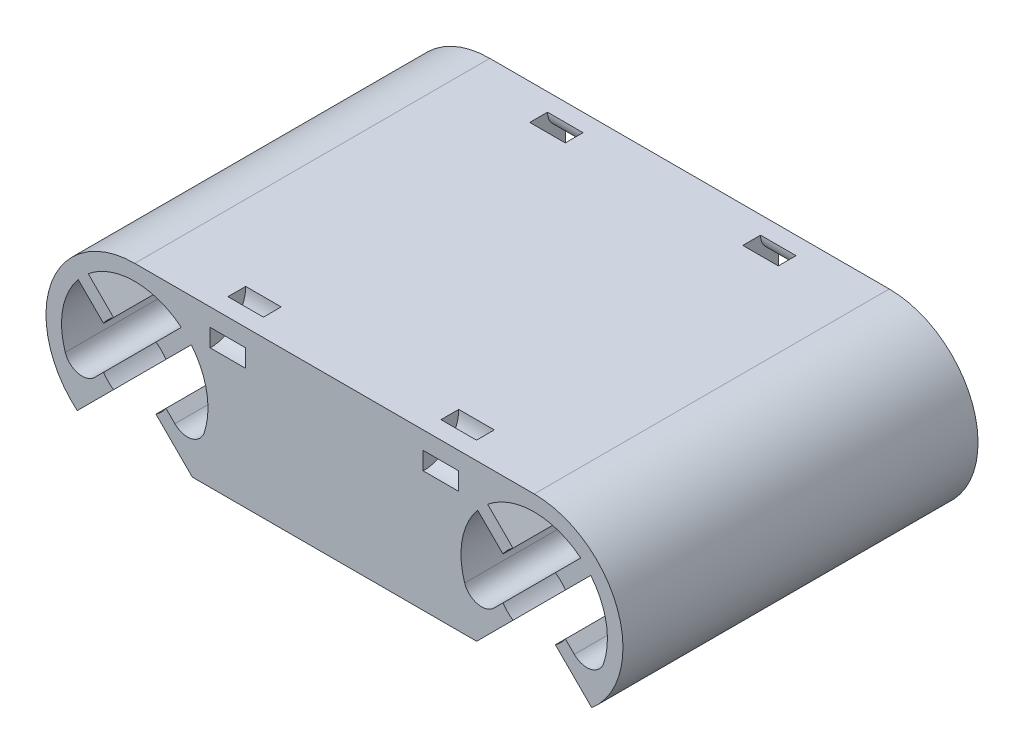
SolidWorks part; units mm, degrees
material "ABS"
ref_plane "Front Plane" through (0, 0, 0) normal (0, 0, 1) x (1, 0, 0)
ref_plane "Top Plane" through (0, 0, 0) normal (0, 1, 0) x (1, 0, 0)
ref_plane "Right Plane" through (0, 0, 0) normal (1, 0, 0) x (0, 0, -1)
sketch "Sketch1" plane through (0, 0, 0) normal (0, 0, 1) x (1, 0, 0)
  line L0 (-18.9828, 2.3858) -> (-16.1282, 5.2405)
  line L1 (-16.0173, -7.6141) -> (16.0173, -7.6141)
  line L2 (-20.1142, 3.5172) -> (-17.2595, 6.3718)
  line L3 (-24.8858, 3.5172) -> (-27.7405, 6.3718)
  line L4 (-26.0172, 2.3858) -> (-28.8718, 5.2405)
  line L5 (-26.0172, -2.3858) -> (-27.0168, -3.3854)
  line L6 (24.8858, 3.5172) -> (27.7405, 6.3718)
  line L7 (20.1142, -3.5172) -> (16.0173, -7.6141)
  line L8 (20.1142, 3.5172) -> (17.2595, 6.3718)
  line L9 (26.0172, 2.3858) -> (28.8718, 5.2405)
  line L10 (18.9828, -2.3858) -> (17.9832, -3.3854)
  line L11 (26.0172, -2.3858) -> (27.0168, -3.3854)
  line L12 (18.9828, 2.3858) -> (16.1282, 5.2405)
  line L13 (24.8858, -3.5172) -> (28.9827, -7.6141)
  line L14 (-24.8858, -3.5172) -> (-28.9827, -7.6141)
  line L15 (-20.1142, -3.5172) -> (-16.0173, -7.6141)
  line L16 (-18.9828, -2.3858) -> (-17.9832, -3.3854)
  line L17 (-22.5, 10) -> (22.5, 10)
  arc A0 (-26.0172, -2.3858) -> (-24.8858, -3.5172) centre (-22.5, 0) ccw
  arc A1 (-22.5, 10) -> (-28.9827, -7.6141) centre (-22.5, 0) ccw
  arc A2 (-28.8718, 5.2405) -> (-30.3289, -2.602) centre (-22.5, 0) ccw
  arc A3 (-24.8858, 3.5172) -> (-26.0172, 2.3858) centre (-22.5, 0) ccw
  arc A4 (-18.9828, 2.3858) -> (-20.1142, 3.5172) centre (-22.5, 0) ccw
  arc A5 (-20.1142, -3.5172) -> (-18.9828, -2.3858) centre (-22.5, 0) ccw
  arc A6 (26.0172, 2.3858) -> (24.8858, 3.5172) centre (22.5, 0) ccw
  arc A7 (-17.2595, 6.3718) -> (-27.7405, 6.3718) centre (-22.5, 0) ccw
  arc A8 (30.3289, -2.602) -> (27.0168, -3.3854) centre (28.431, -1.9712) cw
  arc A9 (-14.6711, -2.602) -> (-16.1282, 5.2405) centre (-22.5, 0) ccw
  arc A10 (28.9827, -7.6141) -> (22.5, 10) centre (22.5, 0) ccw
  arc A11 (14.6711, -2.602) -> (17.9832, -3.3854) centre (16.569, -1.9712) ccw
  arc A12 (20.1142, 3.5172) -> (18.9828, 2.3858) centre (22.5, 0) ccw
  arc A13 (24.8858, -3.5172) -> (26.0172, -2.3858) centre (22.5, 0) ccw
  arc A14 (18.9828, -2.3858) -> (20.1142, -3.5172) centre (22.5, 0) ccw
  arc A15 (-14.6711, -2.602) -> (-17.9832, -3.3854) centre (-16.569, -1.9712) cw
  arc A16 (27.7405, 6.3718) -> (17.2595, 6.3718) centre (22.5, 0) ccw
  arc A17 (30.3289, -2.602) -> (28.8718, 5.2405) centre (22.5, 0) ccw
  arc A18 (16.1282, 5.2405) -> (14.6711, -2.602) centre (22.5, 0) ccw
  arc A19 (-27.0168, -3.3854) -> (-30.3289, -2.602) centre (-28.431, -1.9712) cw
  dimension "D1" = 2
extrude "Boss-Extrude1" add sketch "Sketch1" along normal blind 40
sketch "Sketch2" plane through (0, 0, 0) normal (1, 0, 0) x (0, 0, -1)
  line L0 (-40, 6) -> (-40, 8)
  line L1 (-38, 10) -> (-36, 10)
  line L4 (-2, 10) -> (-4, 10)
  line L5 (0, 6) -> (0, 8)
  arc A0 (-40, 8) -> (-38, 10) centre (-40, 10) ccw
  arc A1 (-40, 6) -> (-36, 10) centre (-40, 10) ccw
  arc A2 (0, 6) -> (-4, 10) centre (0, 10) cw
  arc A3 (0, 8) -> (-2, 10) centre (0, 10) cw
extrude "Cut-Extrude1" [suppressed] cut sketch "Sketch2" against normal blind 1.25 and the other way blind 1.25
sketch "Sketch3" plane through (0, 0, 40) normal (0, 0, 1) x (1, 0, 0)
  line L4 (12, 8) -> (10, 8)
  line L5 (10, 8) -> (10, 6)
  line L6 (10, 6) -> (14, 6)
  line L7 (14, 6) -> (14, 8)
  line L8 (14, 8) -> (12, 8)
  line L9 (-14, 8) -> (-12, 8)
  line L10 (-14, 6) -> (-14, 8)
  line L11 (-10, 6) -> (-14, 6)
  line L12 (-10, 8) -> (-10, 6)
  line L13 (-12, 8) -> (-10, 8)
revolve "Cut-Revolve1" cut sketch "Sketch3" angle 360 about axis through (-22.5, 10, 40) along (-1, 0, 0)
ref_plane "Plane1" through (0, 0, 20) normal (0, 0, 1) x (1, 0, 0)
mirror "Mirror1" about plane through (0, 0, 20) normal (0, 0, 1) of "Cut-Revolve1"
